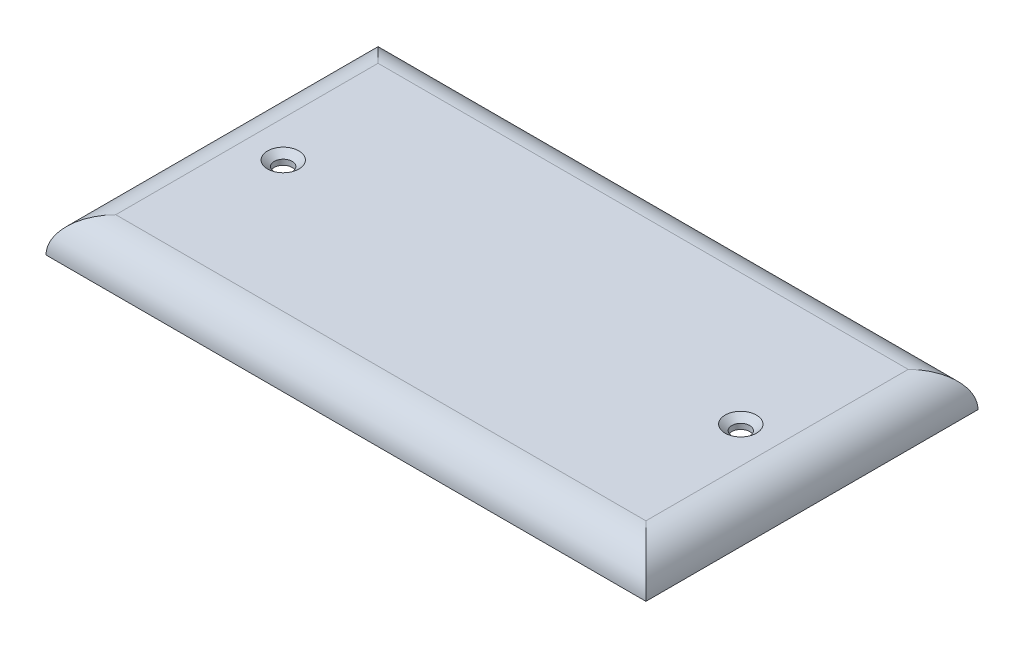
SolidWorks part; units mm, degrees
ref_plane "Front Plane" through (0, 0, 0) normal (0, 0, 1) x (1, 0, 0)
ref_plane "Top Plane" through (0, 0, 0) normal (0, 1, 0) x (1, 0, 0)
ref_plane "Right Plane" through (0, 0, 0) normal (1, 0, 0) x (0, 0, -1)
sketch "Sketch2" plane through (0, 0, 0) normal (0, 1, 0) x (1, 0, 0)
  line L1 (-54.61, -30.226) -> (54.61, -30.226)
  line L2 (-54.61, -30.226) -> (-54.61, 30.226)
  line L3 (-54.61, 30.226) -> (54.61, 30.226)
  line L4 (54.61, -30.226) -> (54.61, 30.226)
  line L5 (-54.61, -30.226) -> (54.61, 30.226) construction
  line L6 (-54.61, 30.226) -> (54.61, -30.226) construction
  point P0 (0, 0)
  dimension "D1" = 109.22
  dimension "D2" = 60.452
extrude "Boss-Extrude1" add sketch "Sketch2" along normal mid plane 6.35
fillet "Fillet3" radius 6.35 4 edges at (-54.61, 3.175, 0) (0, 3.175, -30.226) (54.61, 3.175, 0) (0, 3.175, 30.226)
shell "Shell1" thickness 2 removed face at (0, -3.175, 0)
hole_wizard "CSK for #4 Flat Head Machine Screw (100)1" positions "Sketch4" profile "Sketch3" countersink size "#4" standard "ANSI Inch" end condition through all
sketch "Sketch4" plane through (0, 3.175, 0) normal (0, 1, 0) x (1, 0, 0)
  line L1 (-3.4925, 0) -> (3.4925, 0) construction
  point P0 (41.65, 0)
  dimension "D1" = 41.65
sketch "Sketch3" plane through (41.65, 3.175, 0) normal (1, 0, 0) x (0, 0, 1)
  line L0 (0, 0) -> (0, 6.35)
  line L1 (0, 6.35) -> (1.6319, 6.35)
  line L2 (1.6319, 6.35) -> (1.6319, 1.0284)
  line L3 (1.6319, 1.0284) -> (2.8575, 0)
  line L5 (2.8575, 0) -> (0, 0)
  line L6 (-1.6319, 1.0284) -> (-2.8575, 0) construction
  line L11 (0, -6.35) -> (0, 107.95) construction
  dimension "Thru Hole Dia." = 3.2639
  dimension "Thru Hole Depth" = 6.35
  dimension "Near C'Sink Dia." = 5.715
  dimension "Near C'Sink Angle" = 100
mirror "Mirror1" about plane through (0, 0, 0) normal (1, 0, 0) of "CSK for #4 Flat Head Machine Screw (100)1"
